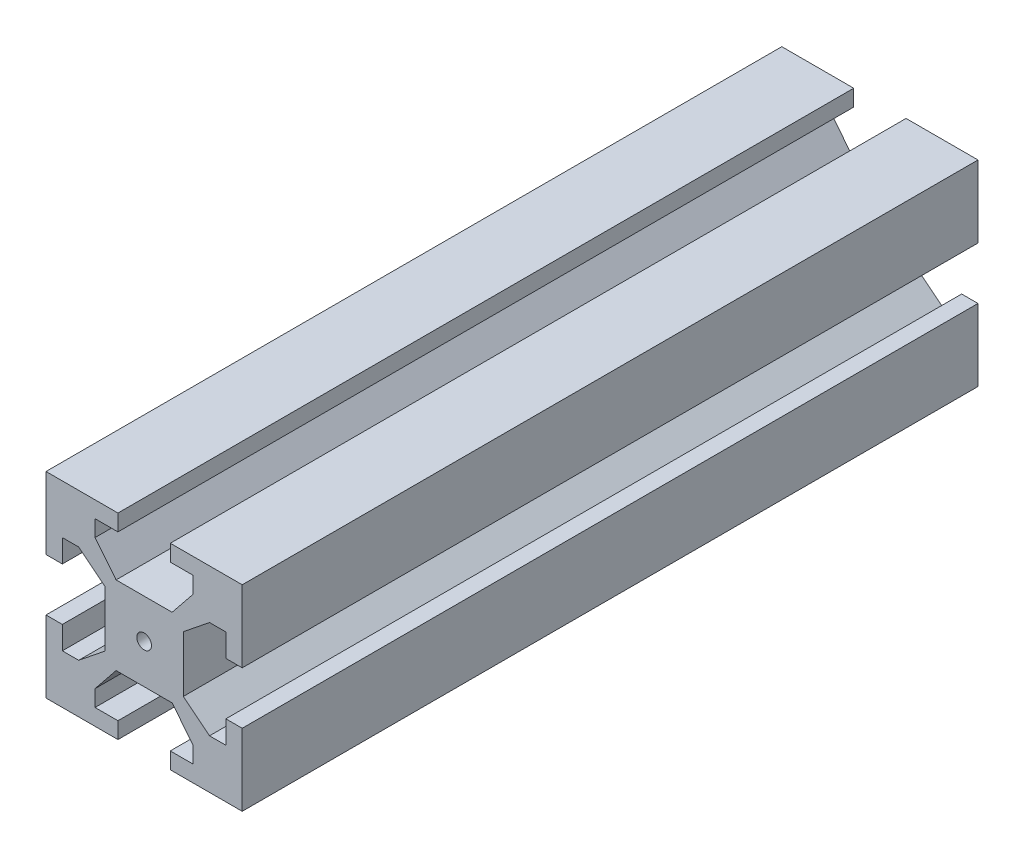
SolidWorks part; units mm, degrees
ref_plane "Front Plane" through (0, 0, 0) normal (0, 0, 1) x (1, 0, 0)
ref_plane "Top Plane" through (0, 0, 0) normal (0, 1, 0) x (1, 0, 0)
ref_plane "Right Plane" through (0, 0, 0) normal (1, 0, 0) x (0, 0, -1)
sketch "Sketch1" plane through (0, 0, 0) normal (0, 0, 1) x (1, 0, 0)
  line L1 (20, 20) -> (5.3333, 20)
  line L2 (20, 20) -> (20, 5.3333)
  line L3 (20, -20) -> (5.3333, -20)
  line L4 (-20, 20) -> (-20, 5.3333)
  line L6 (16.6667, -5.3333) -> (20, -5.3333)
  line L7 (20, 0) -> (8, 0) construction
  line L8 (20, -5.3333) -> (20, -20)
  line L9 (20, 5.3333) -> (20, 0) construction
  line L10 (20, 0) -> (20, -5.3333) construction
  line L11 (16.6667, -5.3333) -> (16.6667, -10)
  line L12 (16.6667, -10) -> (13.3333, -10)
  line L13 (13.3333, -10) -> (8, -5.7143)
  line L14 (8, -5.7143) -> (8, 5.7143)
  line L16 (10, -13.3333) -> (5.7143, -8)
  line L17 (16.6667, 5.3333) -> (20, 5.3333)
  line L18 (16.6667, 5.3333) -> (16.6667, 10)
  line L19 (16.6667, 10) -> (13.3333, 10)
  line L20 (13.3333, 10) -> (8, 5.7143)
  line L21 (-20, 0) -> (20, 0) construction
  line L22 (-5.7143, -8) -> (5.7143, -8)
  line L23 (-10, -13.3333) -> (-5.7143, -8)
  line L24 (-10, -16.6667) -> (-10, -13.3333)
  line L25 (-5.3333, -16.6667) -> (-10, -16.6667)
  line L26 (-5.3333, -16.6667) -> (-5.3333, -20)
  line L27 (5.3333, -16.6667) -> (5.3333, -20)
  line L28 (5.3333, -16.6667) -> (10, -16.6667)
  line L29 (10, -16.6667) -> (10, -13.3333)
  line L30 (-13.3333, -10) -> (-8, -5.7143)
  line L31 (-8, 5.7143) -> (-8, -5.7143)
  line L32 (-13.3333, 10) -> (-8, 5.7143)
  line L33 (-16.6667, 10) -> (-13.3333, 10)
  line L34 (-16.6667, 5.3333) -> (-16.6667, 10)
  line L35 (-16.6667, 5.3333) -> (-20, 5.3333)
  line L36 (-16.6667, -5.3333) -> (-20, -5.3333)
  line L37 (-16.6667, -5.3333) -> (-16.6667, -10)
  line L38 (-16.6667, -10) -> (-13.3333, -10)
  line L39 (-10, 13.3333) -> (-5.7143, 8)
  line L40 (5.7143, 8) -> (-5.7143, 8)
  line L41 (10, 13.3333) -> (5.7143, 8)
  line L42 (10, 16.6667) -> (10, 13.3333)
  line L43 (5.3333, 16.6667) -> (10, 16.6667)
  line L44 (5.3333, 16.6667) -> (5.3333, 20)
  line L45 (-5.3333, 16.6667) -> (-5.3333, 20)
  line L46 (-5.3333, 16.6667) -> (-10, 16.6667)
  line L47 (-10, 16.6667) -> (-10, 13.3333)
  line L48 (-5.3333, 20) -> (-20, 20)
  line L49 (5.3333, 20) -> (-5.3333, 20) construction
  line L50 (-20, -5.3333) -> (-20, -20)
  line L51 (-20, 5.3333) -> (-20, 0) construction
  line L52 (-20, 0) -> (-20, -5.3333) construction
  line L53 (-5.3333, -20) -> (-20, -20)
  line L54 (5.3333, -20) -> (-5.3333, -20) construction
  circle A0 centre (0, 0) radius 1.5
  point P6 (0, 0)
  point P54 (-8, 0)
  dimension "D7" = 3
  dimension "D2" = 40
  dimension "D1" = 10.6667
  dimension "D3" = 3.3333
  dimension "D4" = 12
  dimension "D5" = 5.7143
  dimension "D6" = 10
  dimension "D9" = 4
extrude "Boss-Extrude1" add sketch "Sketch1" along normal mid plane 150
ref_axis "Axis1" through (0, 0, -101.6417) along (0, 0, 1)
equation "\"var1\"=40"
equation "\"D2@Sketch1\"=\"var1\""
equation "\"D1@Sketch1\"=\"var1\"/3.75"
equation "\"D3@Sketch1\"=\"var1\"/12"
equation "\"D4@Sketch1\"=\"var1\"*0.3"
equation "\"D5@Sketch1\"=\"var1\"/7"
equation "\"D6@Sketch1\"=\"var1\"/4"
